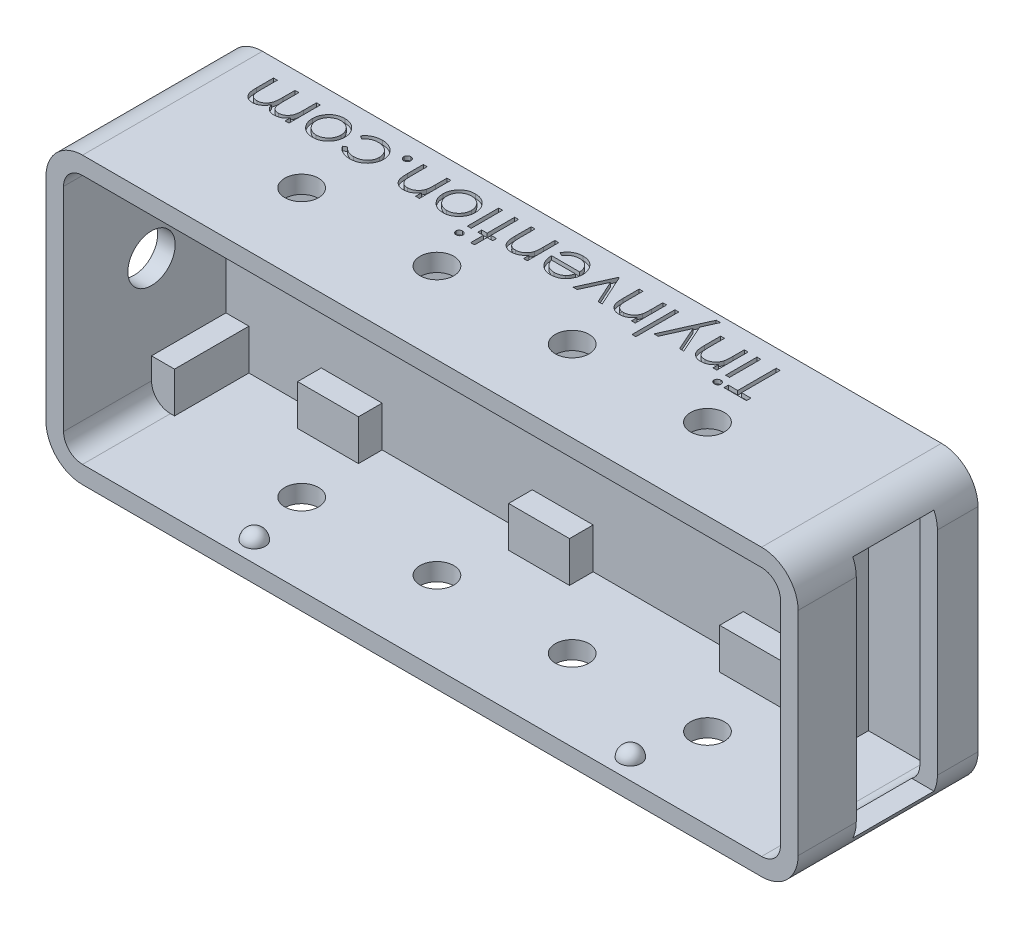
SolidWorks part; units mm, degrees
material "PLA"
ref_plane "Front Plane" through (0, 0, 0) normal (0, 0, 1) x (1, 0, 0)
ref_plane "Top Plane" through (0, 0, 0) normal (0, 1, 0) x (1, 0, 0)
ref_plane "Right Plane" through (0, 0, 0) normal (1, 0, 0) x (0, 0, -1)
sketch "Sketch2" plane through (0, 0, 0) normal (0, 0, 1) x (1, 0, 0)
  line L1 (2.4, -43.153) -> (-47.8, -43.153)
  line L2 (3.8, -44.553) -> (3.8, -60.253)
  line L3 (2.4, -61.653) -> (-47.8, -61.653)
  line L4 (-49.2, -44.553) -> (-49.2, -60.253)
  arc A0 (3.8, -44.553) -> (2.4, -43.153) centre (2.4, -44.553) ccw
  arc A1 (2.4, -61.653) -> (3.8, -60.253) centre (2.4, -60.253) ccw
  arc A2 (-49.2, -60.253) -> (-47.8, -61.653) centre (-47.8, -60.253) ccw
  arc A3 (-49.2, -44.553) -> (-47.8, -43.153) centre (-47.8, -44.553) cw
  point P2 (3.8, -43.153)
  point P9 (-49.2, -61.653)
  point P14 (-49.2, -43.153)
  dimension "D1" = 18.5
  dimension "D3" = 1.4
  dimension "D2" = 53
extrude "Boss-Extrude1" add sketch "Sketch2" along normal blind 12 contours L2 A1 L3 A2 L4 A3 L1 A0
shell "Shell1" thickness 1.3 removed face at (-22.7, -52.403, 12) outward yes
sketch "Sketch3" plane through (0, -61.653, 0) normal (0, 1, 0) x (1, 0, 0)
  line L0 (-9.6, -10.5) -> (-8, -10.5)
  line L1 (2.4, -12) -> (-47.8, -12) construction
  line L2 (5.1, -12) -> (5.1, 1.3) construction
  arc A0 (-8, -10.5) -> (-9.6, -10.5) centre (-8.8, -10.5) ccw
  dimension "D4" = 0.8
  dimension "D1" = 1.5
  dimension "D2" = 13.9
  dimension "D3" = 1.6
revolve "Revolve1" add sketch "Sketch3" angle 360 about L0
ref_plane "Plane1" through (0, -52.403, 0) normal (0, 1, 0) x (1, 0, 0)
mirror "Mirror1" about plane through (0, -52.403, 0) normal (0, 1, 0) of "Revolve1"
sketch "Sketch9" plane through (0, 0, 0) normal (0, 0, 1) x (1, 0, 0)
  line L0 (-47.5, -61.653) -> (-47.5, -58.653)
  line L1 (2.4, -61.653) -> (-47.8, -61.653) construction
  line L2 (2.4, -43.153) -> (-47.8, -43.153) construction
  line L3 (-49.2, -44.553) -> (-49.2, -60.253) construction
  line L4 (-47.5, -58.653) -> (-49.2, -58.653)
  line L8 (2.4, -43.153) -> (-47.8, -43.153)
  line L9 (-49.2, -44.553) -> (-49.2, -60.253)
  line L10 (-47.8, -61.653) -> (2.4, -61.653)
  line L11 (3.8, -60.253) -> (3.8, -44.553)
  line L12 (-47.2, -43.153) -> (-47.8, -43.153)
  line L13 (-49.2, -44.553) -> (-49.2, -60.253)
  line L14 (-47.8, -61.653) -> (-47.5, -61.653)
  arc A4 (3.8, -44.553) -> (2.4, -43.153) centre (2.4, -44.553) ccw
  arc A5 (-47.8, -43.153) -> (-49.2, -44.553) centre (-47.8, -44.553) ccw
  arc A6 (-49.2, -60.253) -> (-47.8, -61.653) centre (-47.8, -60.253) ccw
  arc A7 (2.4, -61.653) -> (3.8, -60.253) centre (2.4, -60.253) ccw
  arc A9 (-47.8, -43.153) -> (-49.2, -44.553) centre (-47.8, -44.553) ccw
  arc A10 (-49.2, -60.253) -> (-47.8, -61.653) centre (-47.8, -60.253) ccw
  line M4 (-49.2, -44.553) -> (-49.2, -60.253)
  arc M5 (-49.2, -60.253) -> (-47.8, -61.653) centre (-47.8, -60.253) ccw
  line M6 (-47.8, -61.653) -> (2.4, -61.653)
  dimension "D1" = 1.7
  dimension "D3" = 3
  dimension "D2" = 0
extrude "Boss-Extrude3" add sketch "Sketch9" along normal blind 5.5 contours L0 L4 M4 M5 M6 region at (-48.3017, -60.0463, 0)
mirror "Mirror2" about plane through (0, -52.403, 0) normal (0, 1, 0) of "Boss-Extrude3"
sketch "Sketch10" plane through (5.1, 0, 0) normal (1, 0, 0) x (0, 0, -1)
  line L0 (6.6, -52.403) -> (-6.6, -52.403) construction
  line L1 (-1.7, -61.403) -> (-7.7, -61.403)
  line L2 (-1.7, -61.403) -> (-1.7, -43.403)
  line L3 (-1.7, -43.403) -> (-7.7, -43.403)
  line L4 (-7.7, -61.403) -> (-7.7, -43.403)
  line L5 (-1.7, -61.403) -> (-7.7, -43.403) construction
  line L6 (-1.7, -43.403) -> (-7.7, -61.403) construction
  line L7 (1.3, -44.553) -> (1.3, -60.253) construction
  point P0 (-4.7, -52.403)
  dimension "D1" = 0
  dimension "D2" = 3
  dimension "D3" = 18
  dimension "D4" = 6
extrude "Cut-Extrude1" cut sketch "Sketch10" against normal blind 2.7
sketch "Sketch11" plane through (0, 0, 0) normal (0, 0, 1) x (1, 0, 0)
  line L0 (6.6, -52.403) -> (-6.6, -52.403) construction
  line L1 (-1.7, -61.653) -> (-3.7, -61.653)
  line L2 (-1.7, -61.653) -> (-1.7, -43.153)
  line L3 (-1.7, -43.153) -> (-3.7, -43.153)
  line L4 (-3.7, -61.653) -> (-3.7, -43.153)
  line L5 (-1.7, -61.653) -> (-3.7, -43.153) construction
  line L6 (-1.7, -43.153) -> (-3.7, -61.653) construction
  line L8 (-50.5, -44.553) -> (-50.5, -60.253) construction
  point P0 (-2.7, -52.403)
  dimension "D1" = 0
  dimension "D2" = 47.8
  dimension "D3" = 2
  dimension "D4" = 18.5
extrude "Boss-Extrude4" add sketch "Sketch11" along normal blind 3.35
ref_plane "Plane2" through (-22.7, 0, 0) normal (-1, 0, 0) x (0, 0, 1)
mirror "Mirror3" about plane through (-22.7, 0, 0) normal (-1, 0, 0) of "Revolve1", "Mirror1"
sketch "Sketch12" plane through (0, 0, 0) normal (0, 0, 1) x (1, 0, 0)
  line L0 (-3.7, -61.653) -> (-47.5, -61.653) construction
  line L1 (-6.45, -61.653) -> (-10.95, -61.653)
  line L2 (-6.45, -61.653) -> (-6.45, -58.653)
  line L3 (-6.45, -58.653) -> (-10.95, -58.653)
  line L4 (-10.95, -61.653) -> (-10.95, -58.653)
  line L5 (-3.7, -43.153) -> (-3.7, -61.653) construction
  dimension "D1" = 3
  dimension "D2" = 4.5
  dimension "D3" = 2.75
extrude "Boss-Extrude5" add sketch "Sketch12" along normal blind 1.75
pattern_linear "LPattern1" count 3 spacing 15.6 along (-1, 0, 0) count 2 spacing 15.5 along (0, 1, 0) of "Boss-Extrude5"
sketch "Sketch19" plane through (0, -41.853, 0) normal (0, 1, 0) x (1, 0, 0)
  line L0 (-7.4973, 0) -> (-45.0839, 0) construction
  text T0 "TinyInvention.com"
extrude "Cut-Extrude4" cut sketch "Sketch19" against normal blind 0.3
sketch "Sketch21" plane through (0, -62.953, 0) normal (0, -1, 0) x (1, 0, 0)
  line L0 (-45.043, 0) -> (0, 0) construction
  text T0 "MinimOSD V1.1 Enclosure" font "Century Gothic" height in points 10
extrude "Cut-Extrude5" cut sketch "Sketch21" against normal blind 0.3
sketch "Sketch22" plane through (0, 0, -1.3) normal (0, 0, -1) x (-1, 0, 0)
  line L1 (3.7, -43.153) -> (3.7, -61.653) construction
  circle A0 centre (11.7, -51.9812) radius 1.75
  dimension "D2" = 3.5
  dimension "D1" = 8
extrude "Cut-Extrude6" cut sketch "Sketch22" against normal blind 1.3
pattern_linear "LPattern2" count 4 spacing 10 along (-1, 0, 0) of "Cut-Extrude6"
sketch "Sketch23" plane through (-50.5, 0, 0) normal (-1, 0, 0) x (0, 0, 1)
  line L0 (12, -44.553) -> (12, -60.253) construction
  line L2 (12, -61.653) -> (5.5, -61.653) construction
  circle A0 centre (5.5, -52.403) radius 1.75
  dimension "D3" = 3.5
  dimension "D1" = 6.5
  dimension "D2" = 9.25
extrude "Cut-Extrude7" cut sketch "Sketch23" against normal blind 1.3
sketch "Sketch24" plane through (0, -41.853, 0) normal (0, 1, 0) x (1, 0, 0)
  line L0 (2.4, -12) -> (2.4, 1.3) construction
  line L1 (2.4, -12) -> (-47.8, -12) construction
  circle A0 centre (-7.6, -6) radius 1.25
  dimension "D1" = 2.5
  dimension "D2" = 10
  dimension "D3" = 6
extrude "Cut-Extrude8" cut sketch "Sketch24" against normal blind 1.3
pattern_linear "LPattern3" count 4 spacing 10 along (-1, 0, 0) count 2 spacing 19.8 along (0, -1, 0) of "Cut-Extrude8"
equation "\"D1@Boss-Extrude1\" = \"BoxDepth\"'depth"
equation "\"D1@Shell1\"=\"WallThickness\""
equation "\"BoxWidth\"= 18.5mm'inner width"
equation "\"D1@Sketch2\"=\"BoxWidth\""
equation "\"BoxLength\"= 53mm'inner length"
equation "\"D2@Sketch2\"=\"BoxLength\""
equation "\"D3@Sketch2\" = \"CornerRadius\"'inner corner radius"
equation "\"CornerRadius\"= 1.4mm'inner corner radius"
equation "\"BoxDepth\"= 12mm'inner depth"
equation "\"WallThickness\"= 1.3mm"
equation "\"LatchOffEdge\"= 1.5mm"
equation "\"LatchRadius\"= 0.8mm"
equation "\"D2@Sketch3\"=(\"BoxLength\"+\"WallThickness\"*2)/4"
equation "\"D1@Sketch3\"=\"LatchOffEdge\""
equation "\"D3@Sketch3\"=\"LatchRadius\"*2"
equation "\"D4@Sketch3\"=\"LatchRadius\""
equation "\"PortWidth\"= 18mm"
equation "\"PortHeight\"= 6mm"
equation "\"PortOffsetBottom\"= 3mm"
equation "\"D3@Sketch10\"=\"PortWidth\""
equation "\"D2@Sketch10\"=\"PortOffsetBottom\""
equation "\"D4@Sketch10\"=\"PortHeight\""
equation "\"D1@Cut-Extrude1\"=\"WallThickness\"+\"CornerRadius\""
equation "\"D4@Sketch11\"=\"BoxWidth\""
equation "\"D4@LPattern1\"=\"BoxWidth\"-\"D1@Sketch12\""
equation "\"D1@Cut-Extrude6\"=\"WallThickness\""
equation "\"D2@Sketch23\"=\"BoxWidth\"/2"
equation "\"D1@Cut-Extrude7\"=\"WallThickness\""
equation "\"D1@Cut-Extrude8\"=\"WallThickness\""
equation "\"D4@LPattern3\"=\"BoxWidth\"+\"WallThickness\""
